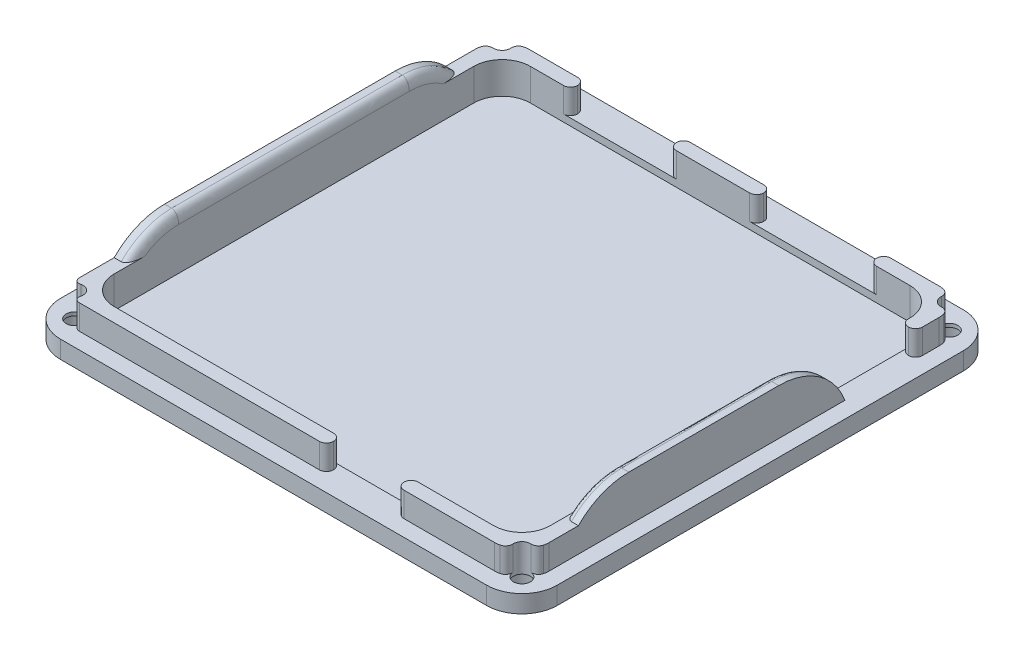
SolidWorks part; units mm, degrees
ref_plane "Ebene vorne" through (0, 0, 0) normal (0, 0, 1) x (1, 0, 0)
ref_plane "Ebene oben" through (0, 0, 0) normal (0, 1, 0) x (1, 0, 0)
ref_plane "Ebene rechts" through (0, 0, 0) normal (1, 0, 0) x (0, 0, -1)
sketch "Skizze1" plane through (0, 0, 0) normal (0, 1, 0) x (1, 0, 0)
  line L1 (-37.8569, 30.2273) -> (32.5181, 30.2273)
  line L2 (-37.8569, 30.2273) -> (-37.8569, -37.3327)
  line L3 (-37.8569, -37.3327) -> (32.5181, -37.3327)
  line L4 (32.5181, 30.2273) -> (32.5181, -37.3327)
  dimension "D1" = 67.56
  dimension "D2" = 70.375
extrude "Aufsatz-Linear austragen1" add sketch "Skizze1" along normal blind 2.5
fillet "Verrundung2" radius 5 4 edges at (-37.8569, 1.25, -30.2273) (32.5181, 1.25, -30.2273) (32.5181, 1.25, 37.3327) (-37.8569, 1.25, 37.3327)
sketch "Skizze2" plane through (0, 2.5, 0) normal (0, 1, 0) x (1, 0, 0)
  line L0 (-35.5569, 25.2273) -> (-32.8569, 27.9273)
  line L1 (27.5181, 27.9273) -> (30.2181, 25.2273)
  line L2 (-35.5569, -32.3327) -> (-32.8569, -35.0327)
  line L3 (27.5181, -35.0327) -> (30.2181, -32.3327)
  line L8 (27.5181, 27.9273) -> (-32.8569, 27.9273)
  line L9 (-35.5569, 25.2273) -> (-35.5569, -32.3327)
  line L10 (-32.8569, -35.0327) -> (27.5181, -35.0327)
  line L11 (30.2181, -32.3327) -> (30.2181, 25.2273)
  line L12 (27.5181, 27.9273) -> (-32.8569, 27.9273)
  line L13 (-35.5569, 25.2273) -> (-35.5569, -32.3327)
  line L14 (-32.8569, -35.0327) -> (27.5181, -35.0327)
  line L15 (30.2181, -32.3327) -> (30.2181, 25.2273)
  line L20 (27.5181, 25.9273) -> (-32.8569, 25.9273)
  line L21 (-33.5569, 25.2273) -> (-33.5569, -32.3327)
  line L22 (-32.8569, -33.0327) -> (27.5181, -33.0327)
  line L23 (28.2181, -32.3327) -> (28.2181, 25.2273)
  line L24 (24.2181, 25.9273) -> (-29.5569, 25.9273)
  line L25 (-33.5569, 21.9273) -> (-33.5569, -29.0327)
  line L26 (-29.5569, -33.0327) -> (24.2181, -33.0327)
  line L27 (28.2181, -29.0327) -> (28.2181, 21.9273)
  arc A0 (24.2181, -33.0327) -> (28.2181, -29.0327) centre (24.2181, -29.0327) ccw
  arc A1 (-33.5569, -29.0327) -> (-29.5569, -33.0327) centre (-29.5569, -29.0327) ccw
  arc A2 (28.2181, 21.9273) -> (24.2181, 25.9273) centre (24.2181, 21.9273) ccw
  arc A3 (-29.5569, 25.9273) -> (-33.5569, 21.9273) centre (-29.5569, 21.9273) ccw
  arc A8 (-32.8569, 27.9273) -> (-35.5569, 25.2273) centre (-32.8569, 25.2273) ccw
  arc A9 (-35.5569, -32.3327) -> (-32.8569, -35.0327) centre (-32.8569, -32.3327) ccw
  arc A10 (27.5181, -35.0327) -> (30.2181, -32.3327) centre (27.5181, -32.3327) ccw
  arc A11 (30.2181, 25.2273) -> (27.5181, 27.9273) centre (27.5181, 25.2273) ccw
  arc A20 (-32.8569, 25.9273) -> (-33.5569, 25.2273) centre (-32.8569, 25.2273) ccw
  arc A21 (-33.5569, -32.3327) -> (-32.8569, -33.0327) centre (-32.8569, -32.3327) ccw
  arc A22 (27.5181, -33.0327) -> (28.2181, -32.3327) centre (27.5181, -32.3327) ccw
  arc A23 (28.2181, 25.2273) -> (27.5181, 25.9273) centre (27.5181, 25.2273) ccw
  dimension "D3" = 4
  dimension "D1" = 2.3
  dimension "D2" = 4.3
extrude "Aufsatz-Linear austragen2" add sketch "Skizze2" along normal blind 3.5 and the other way up to surface (2.5 mm away) other way up to face at (-2.6694, 0, 3.5527)
hole_wizard "CBORE for M2 Hex Socket Head Cap Screw1" positions "Sketch1" profile "Sketch3" counterbore size "M2" standard "DIN" end condition through all
sketch "Sketch1" plane through (0, 0, 0) normal (0, -1, 0) x (-1, 0, 0)
  line L0 (37.8569, 25.2273) -> (37.8569, -32.3327) construction
  line L1 (32.8569, -37.3327) -> (-27.5181, -37.3327) construction
  line L2 (-27.5181, 30.2273) -> (32.8569, 30.2273) construction
  line L3 (-32.5181, -32.3327) -> (-32.5181, 25.2273) construction
  point P0 (34.3569, -33.8327)
  point P2 (-29.0181, -33.8327)
  point P4 (-29.0181, 26.7273)
  point P6 (34.3569, 26.7273)
  dimension "D1" = 3.5
  dimension "D2" = 3.5
  dimension "D3" = 3.5
  dimension "D4" = 3.5
sketch "Sketch3" plane through (-34.3569, 0, 33.8327) normal (1, 0, 0) x (0, 0, -1)
  line L0 (0, 0) -> (0, 6)
  line L1 (0, 6) -> (1.2, 6)
  line L3 (1.2, 6) -> (1.2, 2)
  line L4 (1.2, 2) -> (2.2, 2)
  line L5 (2.2, 2) -> (2.2, 0)
  line L7 (2.2, 0) -> (0, 0)
  line L11 (0, -6.35) -> (0, 107.95) construction
  dimension "Thru Hole Dia." = 2.4
  dimension "Thru Hole Depth" = 6
  dimension "C'Bore Dia." = 4.4
  dimension "C'Bore Depth" = 2
sketch "Sketch4" plane through (0, 2.5, 0) normal (0, 1, 0) x (1, 0, 0)
  line L0 (-33.5569, 21.9273) -> (-33.5569, -29.0327) construction
  line L1 (-29.5569, 25.9273) -> (24.2181, 25.9273)
  line L2 (-33.5569, 21.9273) -> (-33.5569, -29.0327)
  line L3 (-29.5569, -33.0327) -> (24.2181, -33.0327)
  line L4 (28.2181, 21.9273) -> (28.2181, -29.0327)
  line L5 (24.2181, 25.9273) -> (-29.5569, 25.9273) construction
  line L6 (28.2181, -29.0327) -> (28.2181, 21.9273) construction
  line L7 (-29.5569, -33.0327) -> (24.2181, -33.0327) construction
  arc A5 (-29.5569, -33.0327) -> (-33.5569, -29.0327) centre (-29.5569, -29.0327) cw
  arc A6 (28.2181, -29.0327) -> (24.2181, -33.0327) centre (24.2181, -29.0327) cw
  arc A7 (28.2181, 21.9273) -> (24.2181, 25.9273) centre (24.2181, 21.9273) ccw
  arc A8 (-33.5569, 21.9273) -> (-29.5569, 25.9273) centre (-29.5569, 21.9273) cw
  dimension "D1" = 4
extrude "Cut-Extrude1" cut sketch "Sketch4" against normal offset from surface (1 mm away) 1.5 up to face at (-34.3569, 0, 31.6327)
fillet "Fillet2" radius 3 6 edges at (27.5181, 4.25, 35.0327) (30.2181, 4.25, 32.3327) (30.2181, 4.25, -25.2273) (27.5181, 4.25, -27.9273) (-35.5569, 4.25, -25.2273) (-32.8569, 4.25, -27.9273)
sketch "Sketch5" plane through (0, 6, 0) normal (0, 1, 0) x (1, 0, 0)
  line L0 (26.3525, 27.9273) -> (-31.6913, 27.9273) construction
  line L1 (2.5181, 25.9273) -> (18.5181, 25.9273)
  line L2 (2.5181, 25.9273) -> (2.5181, 27.9273)
  line L3 (2.5181, 27.9273) -> (18.5181, 27.9273)
  line L4 (18.5181, 25.9273) -> (18.5181, 27.9273)
  line L5 (-29.5569, 25.9273) -> (24.2181, 25.9273) construction
  line L6 (30.2181, -31.1671) -> (30.2181, 24.0616) construction
  line L7 (26.3525, 27.9273) -> (-31.6913, 27.9273) construction
  line L8 (-23.8569, 27.9273) -> (-9.8569, 27.9273)
  line L9 (-23.8569, 27.9273) -> (-23.8569, 21.9273)
  line L10 (-23.8569, 21.9273) -> (-9.8569, 21.9273)
  line L11 (-9.8569, 27.9273) -> (-9.8569, 21.9273)
  line L12 (-37.8569, 25.2273) -> (-37.8569, -32.3327) construction
  line L13 (2.5181, -33.0327) -> (12.5181, -33.0327)
  line L14 (2.5181, -33.0327) -> (2.5181, -35.0327)
  line L15 (2.5181, -35.0327) -> (12.5181, -35.0327)
  line L16 (12.5181, -33.0327) -> (12.5181, -35.0327)
  line L17 (30.2181, 20.7273) -> (21.6324, 20.7273)
  line L18 (-29.5569, -33.0327) -> (24.2181, -33.0327) construction
  line L19 (-32.8569, -35.0327) -> (26.3525, -35.0327) construction
  line L20 (32.5181, -32.3327) -> (32.5181, 25.2273) construction
  line L21 (30.2181, 20.7273) -> (30.2181, 10.7273)
  line L22 (30.2181, 10.7273) -> (21.6324, 10.7273)
  line L23 (21.6324, 20.7273) -> (21.6324, 10.7273)
  line L24 (27.5181, 30.2273) -> (-32.8569, 30.2273) construction
  point P22 (7.5181, -35.0327)
  point P29 (30.2181, 15.7273)
  dimension "D1" = 16
  dimension "D2" = 14
  dimension "D3" = 28
  dimension "D4" = 25
  dimension "D5" = 10
  dimension "D6" = 14
  dimension "D7" = 10
  dimension "D8" = 14.5
extrude "Cut-Extrude2" cut sketch "Sketch5" against normal up to surface (3.5 mm away) up to face at (-2.732, 2.5, 3.6153)
sketch "Sketch6" plane through (0, 6, 0) normal (0, 1, 0) x (1, 0, 0)
  line L0 (30.2181, -31.1671) -> (30.2181, 10.7273) construction
  line L1 (30.2181, -27.0327) -> (28.2181, -27.0327)
  line L2 (30.2181, -27.0327) -> (30.2181, 10.7273)
  line L3 (30.2181, 10.7273) -> (28.2181, 10.7273)
  line L4 (28.2181, -27.0327) -> (28.2181, 10.7273)
  line L5 (28.2181, -29.0327) -> (28.2181, 10.7273) construction
  line L6 (12.5181, -35.0327) -> (26.3525, -35.0327) construction
  line L7 (26.3525, 27.9273) -> (18.5181, 27.9273) construction
  line L8 (-33.5569, 21.9273) -> (-33.5569, -29.0327) construction
  line L9 (-33.5569, -27.0327) -> (-35.5569, -27.0327)
  line L10 (-33.5569, -27.0327) -> (-33.5569, 19.9273)
  line L11 (-33.5569, 19.9273) -> (-35.5569, 19.9273)
  line L12 (-35.5569, -27.0327) -> (-35.5569, 19.9273)
  line L13 (-35.5569, 24.0616) -> (-35.5569, -32.3327) construction
  line L15 (-32.8569, -35.0327) -> (2.5181, -35.0327) construction
  line L16 (28.2181, 10.7273) -> (30.2181, 10.7273) construction
  point P20 (30.2181, 9.4227)
  dimension "D1" = 8
  dimension "D3" = 8
  dimension "D4" = 8
extrude "Boss-Extrude1" add sketch "Sketch6" along normal blind 3
fillet "Fillet3" radius 10 4 edges at (-34.5569, 9, 27.0327) (29.2181, 9, 27.0327) (-34.5569, 9, -19.9273) (29.2181, 9, -10.7273)
fillet "Fillet4" radius 1.5 6 edges at (28.2181, 7.2158, -7.0607) (28.2181, 8.2195, 23.7643) (28.2181, 9, 9.2658) (-33.5569, 8.2195, 23.7643) (-33.5569, 8.2195, -16.6588) (-33.5569, 9, 3.5527) second distance 1 first distance on face at (28.2181, 5.2185, 0.6878) first distance on face at (-33.5569, 5.8049, 3.5527)
sketch "Sketch7" plane through (0, 0, 0) normal (0, -1, 0) x (1, 0, 0)
  line L0 (-32.8569, 37.3327) -> (27.5181, 37.3327) construction
  line L1 (-37.8569, -25.2273) -> (-37.8569, 32.3327) construction
  line L2 (32.5181, 32.3327) -> (32.5181, -25.2273) construction
  line L3 (27.5181, -30.2273) -> (-32.8569, -30.2273) construction
  circle A0 centre (-27.8569, 32.3327) radius 3.3
  circle A1 centre (22.5181, 32.3327) radius 3.3
  circle A2 centre (-27.8569, -25.2273) radius 3.3
  circle A3 centre (22.5181, -25.2273) radius 3.3
  dimension "D1" = 6.6
  dimension "D2" = 5
  dimension "D3" = 10
  dimension "D4" = 10
  dimension "D5" = 5
extrude "Cut-Extrude3" cut sketch "Sketch7" against normal blind 1
fillet "Verrundung6" radius 1 22 edges at (-23.8569, 4.25, -27.9273) (-23.8569, 4.25, -25.9273) (-33.3717, 4.25, -27.4124) (-35.0421, 4.25, -25.7421) (2.5181, 4.25, 33.0327) (2.5181, 4.25, 35.0327) (12.5181, 4.25, 33.0327) (12.5181, 4.25, 35.0327) (29.7033, 4.25, 32.8476) (28.0329, 4.25, 34.5179) (28.0329, 4.25, -27.4124) (29.7033, 4.25, -25.7421) (28.2181, 4.25, -20.7273) (30.2181, 4.25, -20.7273) (18.5181, 4.25, -25.9273) (18.5181, 4.25, -27.9273) (-9.8569, 4.25, -27.9273) (2.5181, 4.25, -27.9273) (2.5181, 4.25, -25.9273) (-9.8569, 4.25, -25.9273) (-35.5569, 4.25, 32.3327) (-32.8569, 4.25, 35.0327)
fillet "Verrundung7" radius 1 2 edges at (-33.3717, 4.25, 34.5179) (-35.0421, 4.25, 32.8476)
